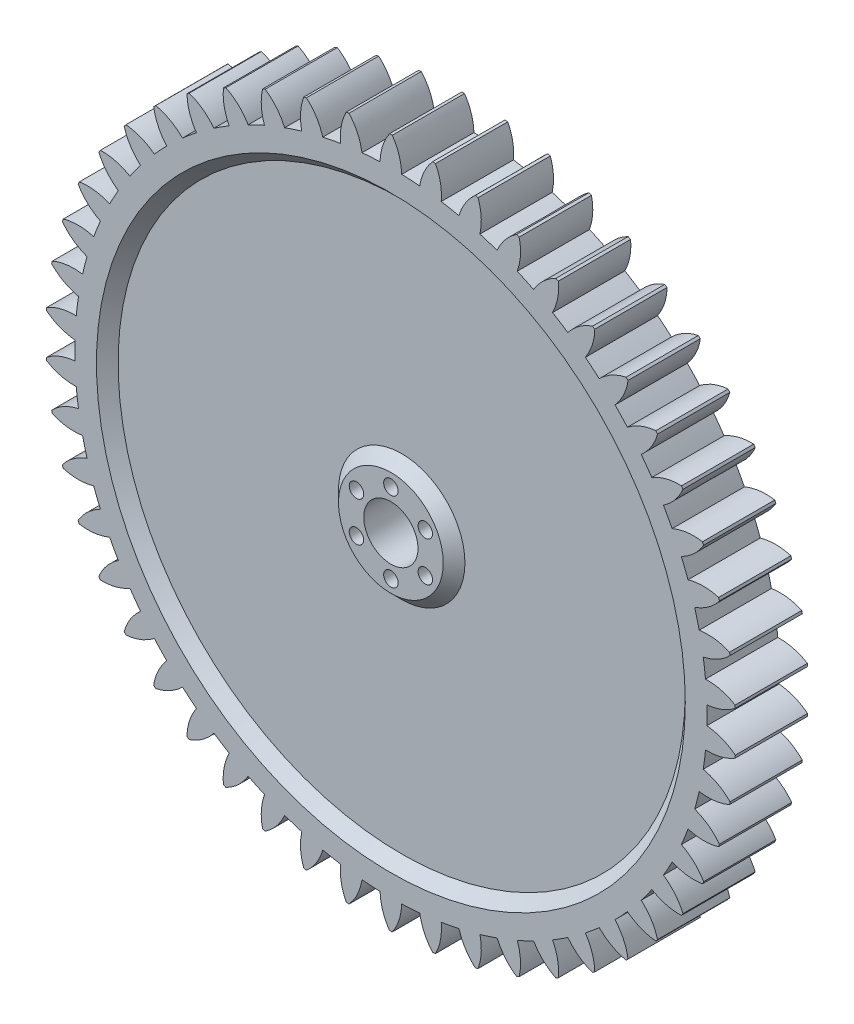
SolidWorks part; units mm, degrees
material "Cast iron, gray, flake graphite, EN GJL 250"
ref_plane "Front Plane" through (0, 0, 0) normal (0, 0, 1) x (1, 0, 0)
ref_plane "Top Plane" through (0, 0, 0) normal (0, 1, 0) x (1, 0, 0)
ref_plane "Right Plane" through (0, 0, 0) normal (1, 0, 0) x (0, 0, -1)
sketch "Sketch8" plane through (0, 0, 0) normal (0, 0, 1) x (1, 0, 0)
  circle A0 centre (0, 0) radius 82.5
  circle A1 centre (0, 0) radius 87.5
  dimension "D1" = 175
  dimension "D2" = 165
extrude "Boss-Extrude1" add sketch "Sketch8" along normal mid plane 20
sketch "Sketch9" plane through (0, 0, 0) normal (0, 0, 1) x (1, 0, 0)
  circle A0 centre (0, 0) radius 13.5
  dimension "D1" = 27
extrude "Boss-Extrude2" add sketch "Sketch9" along normal mid plane 20 separate body
sketch "Sketch10" plane through (0, 0, 0) normal (0, 0, 1) x (1, 0, 0)
  circle A0 centre (0, 0) radius 13.5
  circle A1 centre (0, 0) radius 82.5
  circle A2 centre (0, 0) radius 13.5 construction
  circle A3 centre (0, 0) radius 82.5 construction
extrude "Boss-Extrude3" add sketch "Sketch10" along normal mid plane 14
chamfer "Chamfer2" distance 4 angle 45 4 edges at (82.5, 0, 7) (13.5, 0, 7) (82.5, 0, -7) (13.5, 0, -7)
sketch "Sketch11" plane through (0, 0, 10) normal (0, 0, 1) x (1, 0, 0)
  circle A0 centre (0, 0) radius 7.5
  point P3 (0, 13.4873)
  point P10 (0, 14.5114)
  dimension "D1" = 15
extrude "Cut-Extrude1" cut sketch "Sketch11" against normal through all
ref_axis "Axis1" through (0, 0, -10) along (0, 0, 1)
sketch "Sketch12" plane through (0, 0, 10) normal (0, 0, 1) x (1, 0, 0)
  line L0 (0, 14.5) -> (0, 7.5) construction
  circle A0 centre (0, 0) radius 14.5 construction
  circle A1 centre (0, 0) radius 7.5 construction
  circle A2 centre (0, 11) radius 2
  point P9 (0, 0)
  point P10 (0, 11)
  dimension "D1" = 4
extrude "Cut-Extrude2" cut sketch "Sketch12" against normal through all
pattern_circular "CirPattern1" count 6 over 360 about axis through (0, 0, -10) along (0, 0, 1) of "Cut-Extrude2"
sketch "Sketch13" plane through (0, 0, 10) normal (0, 0, 1) x (1, 0, 0)
  line L0 (-0.375, 95.5) -> (0.375, 95.5)
  line L1 (4.7384, 102.8027) -> (-5.4884, 88.1973) construction
  line L2 (0, 95.5) -> (0, 87.5) construction
  circle A0 centre (0, 0) radius 87.5 construction
  arc A1 (3, 87.4486) -> (-3, 87.4486) centre (0, 0) ccw
  spline S0 degree 2 poles (-3, 87.4486) (-2.8086, 92.0245) (-0.375, 95.5) knots 0 0 0 0.951846 0.951846 0.951846
  spline S1 degree 2 poles (3, 87.4486) (2.8086, 92.0245) (0.375, 95.5) knots 0 0 0 0.951846 0.951846 0.951846
  point P4 (0.5158, 108.8539)
  point P7 (0.3089, 108.3449)
  point P8 (-0.0809, 108.0586)
  point P10 (0, 108.1255)
  point P13 (0, 0)
  point P14 (0, 108.1409)
  point P16 (0, 108.3049)
  point P17 (0, 108.335)
  point P19 (0, 108.35)
  dimension "D1" = 55
  dimension "D3" = 8
  dimension "D4" = 6
  dimension "D5" = 8.4857
  dimension "D2" = 0.75
extrude "Boss-Extrude4" add sketch "Sketch13" against normal up to surface (20 mm away) up to face at (81.5, 0, -10)
pattern_circular "CirPattern2" count 50 over 360 about axis through (0, 0, 10) along (0, 0, -1) of "Boss-Extrude4"
equation "\"Flywheel Diameter\"= 175mm"
equation "\"Crankshaft Radius\"= 15mm"
equation "\"Flywheel Thickness\"= 20mm"
equation "\"D1@Sketch8\"=\"Flywheel Diameter\""
equation "\"D2@Sketch8\"=\"Flywheel Diameter\"-10mm"
equation "\"D1@Boss-Extrude1\"=\"Flywheel Thickness\""
equation "\"Hub Diameter\"= \"Crankshaft Radius\" + 12mm"
equation "\"D1@Sketch9\"=\"Hub Diameter\""
equation "\"D1@Boss-Extrude2\"=\"Flywheel Thickness\""
equation "\"D1@Boss-Extrude3\"=\"Flywheel Thickness\"*0.7"
equation "\"D1@Sketch11\"=\"Crankshaft Radius\""
equation "\"Bolt Hole Diameter\"= 4mm"
equation "\"D1@Sketch12\"=\"Bolt Hole Diameter\""
